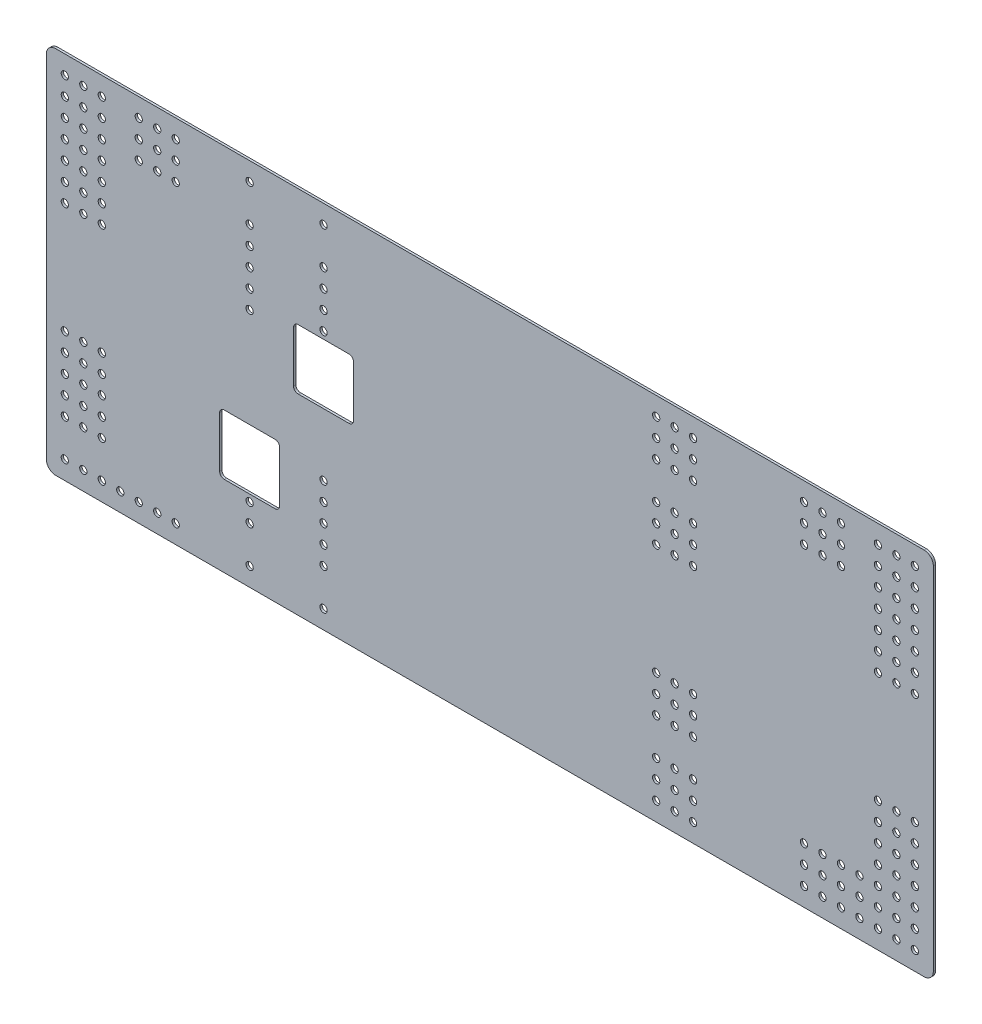
SolidWorks part; units mm, degrees
ref_plane "Front Plane" through (0, 0, 0) normal (0, 0, 1) x (1, 0, 0)
ref_plane "Top Plane" through (0, 0, 0) normal (0, 1, 0) x (1, 0, 0)
ref_plane "Right Plane" through (0, 0, 0) normal (1, 0, 0) x (0, 0, -1)
sketch "Sketch1" plane through (0, 0, 0) normal (0, 0, 1) x (1, 0, 0)
  line L1 (-148.9657, 122.234) -> (447.9343, 122.234)
  line L2 (-155.3157, 115.884) -> (-155.3157, -125.416)
  line L3 (-148.9657, -131.766) -> (447.9343, -131.766)
  line L4 (454.2843, 115.884) -> (454.2843, -125.416)
  arc A0 (-155.3157, -125.416) -> (-148.9657, -131.766) centre (-148.9657, -125.416) ccw
  arc A1 (447.9343, -131.766) -> (454.2843, -125.416) centre (447.9343, -125.416) ccw
  arc A2 (447.9343, 122.234) -> (454.2843, 115.884) centre (447.9343, 115.884) cw
  arc A3 (-148.9657, 122.234) -> (-155.3157, 115.884) centre (-148.9657, 115.884) ccw
  point P6 (-155.3157, -131.766)
  point P11 (454.2843, 122.234)
  point P14 (-155.3157, 122.234)
  dimension "D3" = 6.35
  dimension "D1" = 254
  dimension "D2" = 609.6
extrude "Boss-Extrude1" add sketch "Sketch1" along normal blind 1.5875
sketch "Sketch2" plane through (0, 0, 1.5875) normal (0, 0, 1) x (1, 0, 0)
  line L0 (447.9343, 122.234) -> (-148.9657, 122.234) construction
  line L1 (-155.3157, 115.884) -> (-155.3157, -125.416) construction
  line L2 (-155.3157, -4.766) -> (454.2843, -4.766) construction
  line L3 (454.2843, -125.416) -> (454.2843, 115.884) construction
  line L4 (149.4843, 122.234) -> (149.4843, -131.766) construction
  line L5 (-148.9657, -131.766) -> (447.9343, -131.766) construction
  line L6 (454.2843, -125.416) -> (454.2843, 115.884) construction
  line L7 (447.9343, 122.234) -> (-148.9657, 122.234) construction
  line L8 (-148.9657, -131.766) -> (447.9343, -131.766) construction
  circle A0 centre (-142.6157, 109.534) radius 2.5
  circle A1 centre (-129.9157, 109.534) radius 2.5
  circle A2 centre (-117.2157, 109.534) radius 2.5
  circle A4 centre (-91.8157, 109.534) radius 2.5
  circle A5 centre (-79.1157, 109.534) radius 2.5
  circle A6 centre (-66.4157, 109.534) radius 2.5
  circle A7 centre (-129.9157, 96.834) radius 2.5
  circle A8 centre (-117.2157, 96.834) radius 2.5
  circle A10 centre (-91.8157, 96.834) radius 2.5
  circle A11 centre (-79.1157, 96.834) radius 2.5
  circle A12 centre (-66.4157, 96.834) radius 2.5
  circle A13 centre (-129.9157, 84.134) radius 2.5
  circle A14 centre (-117.2157, 84.134) radius 2.5
  circle A16 centre (-91.8157, 84.134) radius 2.5
  circle A17 centre (-79.1157, 84.134) radius 2.5
  circle A18 centre (-66.4157, 84.134) radius 2.5
  circle A19 centre (-142.6157, 96.834) radius 2.5
  circle A20 centre (-142.6157, 84.134) radius 2.5
  circle A24 centre (-142.6157, 71.434) radius 2.5
  circle A25 centre (-129.9157, 71.434) radius 2.5
  circle A26 centre (-117.2157, 71.434) radius 2.5
  circle A27 centre (-129.9157, 58.734) radius 2.5
  circle A28 centre (-117.2157, 58.734) radius 2.5
  circle A29 centre (-129.9157, 46.034) radius 2.5
  circle A30 centre (-117.2157, 46.034) radius 2.5
  circle A31 centre (-129.9157, 33.334) radius 2.5
  circle A32 centre (-117.2157, 33.334) radius 2.5
  circle A35 centre (-142.6157, 58.734) radius 2.5
  circle A36 centre (-142.6157, 46.034) radius 2.5
  circle A37 centre (-142.6157, 33.334) radius 2.5
  circle A39 centre (-142.6157, -42.866) radius 2.5
  circle A40 centre (-142.6157, -55.566) radius 2.5
  circle A41 centre (-142.6157, -68.266) radius 2.5
  circle A42 centre (-117.2157, -42.866) radius 2.5
  circle A43 centre (-129.9157, -42.866) radius 2.5
  circle A44 centre (-117.2157, -55.566) radius 2.5
  circle A45 centre (-129.9157, -55.566) radius 2.5
  circle A46 centre (-117.2157, -68.266) radius 2.5
  circle A47 centre (-129.9157, -68.266) radius 2.5
  circle A48 centre (-117.2157, -80.966) radius 2.5
  circle A49 centre (-129.9157, -80.966) radius 2.5
  circle A50 centre (-142.6157, -80.966) radius 2.5
  circle A51 centre (-142.6157, -93.666) radius 2.5
  circle A57 centre (-117.2157, -93.666) radius 2.5
  circle A58 centre (-129.9157, -93.666) radius 2.5
  circle A65 centre (-66.4157, -119.066) radius 2.5
  circle A66 centre (-79.1157, -119.066) radius 2.5
  circle A67 centre (-91.8157, -119.066) radius 2.5
  circle A68 centre (-104.5157, -119.066) radius 2.5
  circle A69 centre (-117.2157, -119.066) radius 2.5
  circle A70 centre (-129.9157, -119.066) radius 2.5
  circle A71 centre (-142.6157, -119.066) radius 2.5
  circle A72 centre (441.5843, -119.066) radius 2.5
  circle A73 centre (428.8843, -119.066) radius 2.5
  circle A74 centre (416.1843, -119.066) radius 2.5
  circle A75 centre (403.4843, -119.066) radius 2.5
  circle A76 centre (390.7843, -119.066) radius 2.5
  circle A77 centre (378.0843, -119.066) radius 2.5
  circle A78 centre (365.3843, -119.066) radius 2.5
  circle A79 centre (428.8843, -106.366) radius 2.5
  circle A80 centre (416.1843, -106.366) radius 2.5
  circle A81 centre (403.4843, -106.366) radius 2.5
  circle A82 centre (390.7843, -106.366) radius 2.5
  circle A83 centre (378.0843, -106.366) radius 2.5
  circle A84 centre (365.3843, -106.366) radius 2.5
  circle A85 centre (428.8843, -93.666) radius 2.5
  circle A86 centre (416.1843, -93.666) radius 2.5
  circle A87 centre (403.4843, -93.666) radius 2.5
  circle A88 centre (390.7843, -93.666) radius 2.5
  circle A89 centre (378.0843, -93.666) radius 2.5
  circle A90 centre (365.3843, -93.666) radius 2.5
  circle A91 centre (441.5843, -106.366) radius 2.5
  circle A92 centre (441.5843, -93.666) radius 2.5
  circle A93 centre (441.5843, -80.966) radius 2.5
  circle A94 centre (428.8843, -80.966) radius 2.5
  circle A95 centre (416.1843, -80.966) radius 2.5
  circle A96 centre (428.8843, -68.266) radius 2.5
  circle A97 centre (416.1843, -68.266) radius 2.5
  circle A98 centre (428.8843, -55.566) radius 2.5
  circle A99 centre (416.1843, -55.566) radius 2.5
  circle A100 centre (428.8843, -42.866) radius 2.5
  circle A101 centre (416.1843, -42.866) radius 2.5
  circle A102 centre (441.5843, -68.266) radius 2.5
  circle A103 centre (441.5843, -55.566) radius 2.5
  circle A104 centre (441.5843, -42.866) radius 2.5
  circle A105 centre (441.5843, 33.334) radius 2.5
  circle A106 centre (441.5843, 46.034) radius 2.5
  circle A107 centre (441.5843, 58.734) radius 2.5
  circle A108 centre (416.1843, 33.334) radius 2.5
  circle A110 centre (416.1843, 46.034) radius 2.5
  circle A112 centre (416.1843, 58.734) radius 2.5
  circle A114 centre (416.1843, 71.434) radius 2.5
  circle A116 centre (441.5843, 71.434) radius 2.5
  circle A117 centre (441.5843, 84.134) radius 2.5
  circle A118 centre (441.5843, 96.834) radius 2.5
  circle A119 centre (365.3843, 84.134) radius 2.5
  circle A120 centre (378.0843, 84.134) radius 2.5
  circle A121 centre (390.7843, 84.134) radius 2.5
  circle A123 centre (416.1843, 84.134) radius 2.5
  circle A124 centre (428.8843, 84.134) radius 2.5
  circle A125 centre (365.3843, 96.834) radius 2.5
  circle A126 centre (378.0843, 96.834) radius 2.5
  circle A127 centre (390.7843, 96.834) radius 2.5
  circle A129 centre (416.1843, 96.834) radius 2.5
  circle A130 centre (428.8843, 96.834) radius 2.5
  circle A131 centre (365.3843, 109.534) radius 2.5
  circle A132 centre (378.0843, 109.534) radius 2.5
  circle A133 centre (390.7843, 109.534) radius 2.5
  circle A135 centre (416.1843, 109.534) radius 2.5
  circle A136 centre (428.8843, 109.534) radius 2.5
  circle A137 centre (441.5843, 109.534) radius 2.5
  circle A138 centre (-15.6157, 109.534) radius 2.5
  circle A139 centre (35.1843, 109.534) radius 2.5
  circle A142 centre (-15.6157, 84.134) radius 2.5
  circle A143 centre (35.1843, 84.134) radius 2.5
  circle A144 centre (-15.6157, 71.434) radius 2.5
  circle A145 centre (35.1843, 71.434) radius 2.5
  circle A146 centre (-15.6157, 58.734) radius 2.5
  circle A147 centre (35.1843, 58.734) radius 2.5
  circle A148 centre (-15.6157, 46.034) radius 2.5
  circle A149 centre (35.1843, 46.034) radius 2.5
  circle A150 centre (-15.6157, 33.334) radius 2.5
  circle A151 centre (35.1843, 33.334) radius 2.5
  circle A152 centre (35.1843, -42.866) radius 2.5
  circle A153 centre (-15.6157, -42.866) radius 2.5
  circle A154 centre (35.1843, -55.566) radius 2.5
  circle A155 centre (-15.6157, -55.566) radius 2.5
  circle A156 centre (35.1843, -68.266) radius 2.5
  circle A157 centre (-15.6157, -68.266) radius 2.5
  circle A158 centre (35.1843, -80.966) radius 2.5
  circle A159 centre (-15.6157, -80.966) radius 2.5
  circle A160 centre (35.1843, -93.666) radius 2.5
  circle A161 centre (-15.6157, -93.666) radius 2.5
  circle A164 centre (35.1843, -119.066) radius 2.5
  circle A165 centre (-15.6157, -119.066) radius 2.5
  circle A166 centre (289.1843, 109.534) radius 2.5
  circle A167 centre (276.4843, 109.534) radius 2.5
  circle A168 centre (263.7843, 109.534) radius 2.5
  circle A169 centre (276.4843, 96.834) radius 2.5
  circle A170 centre (263.7843, 96.834) radius 2.5
  circle A171 centre (276.4843, 84.134) radius 2.5
  circle A172 centre (263.7843, 84.134) radius 2.5
  circle A175 centre (276.4843, 58.734) radius 2.5
  circle A176 centre (263.7843, 58.734) radius 2.5
  circle A177 centre (276.4843, 46.034) radius 2.5
  circle A178 centre (263.7843, 46.034) radius 2.5
  circle A179 centre (276.4843, 33.334) radius 2.5
  circle A180 centre (263.7843, 33.334) radius 2.5
  circle A181 centre (289.1843, 96.834) radius 2.5
  circle A182 centre (289.1843, 84.134) radius 2.5
  circle A184 centre (289.1843, 58.734) radius 2.5
  circle A185 centre (289.1843, 46.034) radius 2.5
  circle A186 centre (289.1843, 33.334) radius 2.5
  circle A187 centre (289.1843, -42.866) radius 2.5
  circle A188 centre (289.1843, -55.566) radius 2.5
  circle A189 centre (289.1843, -68.266) radius 2.5
  circle A192 centre (289.1843, -106.366) radius 2.5
  circle A193 centre (263.7843, -42.866) radius 2.5
  circle A194 centre (276.4843, -42.866) radius 2.5
  circle A195 centre (263.7843, -55.566) radius 2.5
  circle A196 centre (276.4843, -55.566) radius 2.5
  circle A197 centre (263.7843, -68.266) radius 2.5
  circle A198 centre (276.4843, -68.266) radius 2.5
  circle A203 centre (263.7843, -106.366) radius 2.5
  circle A204 centre (276.4843, -106.366) radius 2.5
  circle A205 centre (263.7843, -119.066) radius 2.5
  circle A206 centre (276.4843, -119.066) radius 2.5
  circle A207 centre (289.1843, -119.066) radius 2.5
  circle A208 centre (276.4843, 71.434) radius 2.5 [skipped]
  circle A209 centre (263.7843, 71.434) radius 2.5 [skipped]
  circle A210 centre (289.1843, 71.434) radius 2.5 [skipped]
  circle A211 centre (-15.6157, 96.834) radius 2.5 [skipped]
  circle A212 centre (35.1843, 96.834) radius 2.5 [skipped]
  circle A213 centre (-104.5157, 109.534) radius 2.5 [skipped]
  circle A214 centre (-104.5157, 96.834) radius 2.5 [skipped]
  circle A215 centre (-104.5157, 84.134) radius 2.5 [skipped]
  circle A216 centre (428.8843, 71.434) radius 2.5
  circle A217 centre (428.8843, 58.734) radius 2.5
  circle A218 centre (428.8843, 46.034) radius 2.5
  circle A219 centre (428.8843, 33.334) radius 2.5
  circle A220 centre (289.1843, -93.666) radius 2.5
  circle A221 centre (276.4843, -93.666) radius 2.5
  circle A222 centre (263.7843, -93.666) radius 2.5
  dimension "D3" = 5
  dimension "D7" = 5
  dimension "D11" = 5
  dimension "D14" = 5
  dimension "D19" = 5
  dimension "D25" = 5
  dimension "D27" = 38.1
  dimension "D29" = 5
  dimension "D1" = 12.7
  dimension "D2" = 12.7
  dimension "D6" = 50.8
  dimension "D8" = 12.7
  dimension "D12" = 139.7
  dimension "D13" = 12.7
  dimension "D15" = 50.8
  dimension "D16" = 12.7
  dimension "D18" = 165.1
  dimension "D20" = 12.7
  dimension "D23" = 25.4
  dimension "D24" = 50.8
  dimension "D28" = 165.1
  dimension "D4" = 7
  dimension "D5" = 3
  dimension "D9" = 3
  dimension "D10" = 4
  dimension "D17" = 7
  dimension "D21" = 3
  dimension "D22" = 7
  dimension "D26" = 4
extrude "Cut-Extrude1" cut sketch "Sketch2" against normal through all
sketch "Sketch3" plane through (0, 0, 0) normal (0, 0, -1) x (-1, 0, 0)
  line L0 (30.5382, -73.0285) -> (0.6932, -73.0285) construction
  line L1 (-1.8468, -70.4885) -> (-1.8468, -40.6435) construction
  line L2 (0.6932, -38.1035) -> (30.5382, -38.1035) construction
  line L3 (33.0782, -40.6435) -> (33.0782, -70.4885) construction
  line L4 (-20.2618, 3.1715) -> (-50.1068, 3.1715) construction
  line L5 (-52.6468, 5.7115) -> (-52.6468, 35.5565) construction
  line L6 (-50.1068, 38.0965) -> (-20.2618, 38.0965) construction
  line L7 (-17.7218, 35.5565) -> (-17.7218, 5.7115) construction
  line L8 (30.5382, -73.0285) -> (0.6932, -73.0285) construction
  line L9 (-1.8468, -70.4885) -> (-1.8468, -40.6435) construction
  line L10 (0.6932, -38.1035) -> (30.5382, -38.1035) construction
  line L11 (33.0782, -40.6435) -> (33.0782, -70.4885) construction
  line L12 (-20.2618, 3.1715) -> (-50.1068, 3.1715) construction
  line L13 (-52.6468, 5.7115) -> (-52.6468, 35.5565) construction
  line L14 (-50.1068, 38.0965) -> (-20.2618, 38.0965) construction
  line L15 (-17.7218, 35.5565) -> (-17.7218, 5.7115) construction
  line L17 (-1.8468, -34.9285) -> (33.0782, -34.9285)
  line L18 (-5.0218, -38.1035) -> (-5.0218, -73.0285)
  line L19 (-1.8468, -76.2035) -> (33.0782, -76.2035)
  line L20 (36.2532, -38.1035) -> (36.2532, -73.0285)
  line L21 (-52.6468, 41.2715) -> (-17.7218, 41.2715)
  line L22 (-55.8218, 38.0965) -> (-55.8218, 3.1715)
  line L23 (-52.6468, -0.0035) -> (-17.7218, -0.0035)
  line L24 (-14.5468, 38.0965) -> (-14.5468, 3.1715)
  arc A0 (30.5382, -73.0285) -> (33.0782, -70.4885) centre (30.5382, -70.4885) ccw construction
  arc A1 (-1.8468, -70.4885) -> (0.6932, -73.0285) centre (0.6932, -70.4885) ccw construction
  arc A2 (0.6932, -38.1035) -> (-1.8468, -40.6435) centre (0.6932, -40.6435) ccw construction
  arc A3 (33.0782, -40.6435) -> (30.5382, -38.1035) centre (30.5382, -40.6435) ccw construction
  arc A4 (-20.2618, 3.1715) -> (-17.7218, 5.7115) centre (-20.2618, 5.7115) ccw construction
  arc A5 (-52.6468, 5.7115) -> (-50.1068, 3.1715) centre (-50.1068, 5.7115) ccw construction
  arc A6 (-50.1068, 38.0965) -> (-52.6468, 35.5565) centre (-50.1068, 35.5565) ccw construction
  arc A7 (-17.7218, 35.5565) -> (-20.2618, 38.0965) centre (-20.2618, 35.5565) ccw construction
  arc A8 (30.5382, -73.0285) -> (33.0782, -70.4885) centre (30.5382, -70.4885) ccw construction
  arc A9 (-1.8468, -70.4885) -> (0.6932, -73.0285) centre (0.6932, -70.4885) ccw construction
  arc A10 (0.6932, -38.1035) -> (-1.8468, -40.6435) centre (0.6932, -40.6435) ccw construction
  arc A11 (33.0782, -40.6435) -> (30.5382, -38.1035) centre (30.5382, -40.6435) ccw construction
  arc A12 (-20.2618, 3.1715) -> (-17.7218, 5.7115) centre (-20.2618, 5.7115) ccw construction
  arc A13 (-52.6468, 5.7115) -> (-50.1068, 3.1715) centre (-50.1068, 5.7115) ccw construction
  arc A14 (-50.1068, 38.0965) -> (-52.6468, 35.5565) centre (-50.1068, 35.5565) ccw construction
  arc A15 (-17.7218, 35.5565) -> (-20.2618, 38.0965) centre (-20.2618, 35.5565) ccw construction
  arc A16 (-1.8468, -34.9285) -> (-5.0218, -38.1035) centre (-1.8468, -38.1035) ccw
  arc A17 (-5.0218, -73.0285) -> (-1.8468, -76.2035) centre (-1.8468, -73.0285) ccw
  arc A18 (33.0782, -76.2035) -> (36.2532, -73.0285) centre (33.0782, -73.0285) ccw
  arc A19 (33.0782, -34.9285) -> (36.2532, -38.1035) centre (33.0782, -38.1035) cw
  arc A20 (-55.8218, 3.1715) -> (-52.6468, -0.0035) centre (-52.6468, 3.1715) ccw
  arc A21 (-17.7218, -0.0035) -> (-14.5468, 3.1715) centre (-17.7218, 3.1715) ccw
  arc A22 (-17.7218, 41.2715) -> (-14.5468, 38.0965) centre (-17.7218, 38.0965) cw
  arc A23 (-52.6468, 41.2715) -> (-55.8218, 38.0965) centre (-52.6468, 38.0965) ccw
  dimension "D5" = 3.175
  dimension "D8" = 3.175
  dimension "D1" = 3.175
  dimension "D2" = 3.175
  dimension "D3" = 3.175
  dimension "D4" = 3.175
  dimension "D6" = 3.175
  dimension "D7" = 3.175
extrude "Cut-Extrude2" cut sketch "Sketch3" against normal through all
